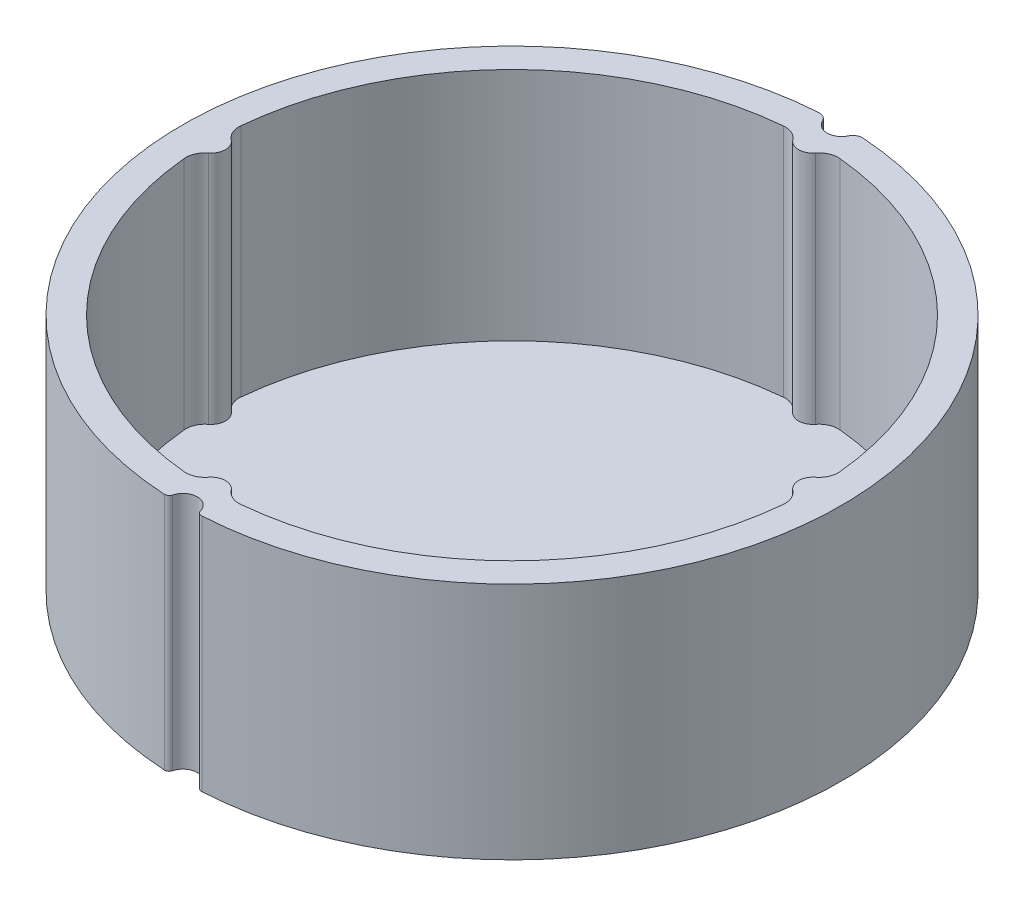
SolidWorks part; units mm, degrees
ref_plane "Front Plane" through (0, 0, 0) normal (0, 0, 1) x (1, 0, 0)
ref_plane "Top Plane" through (0, 0, 0) normal (0, 1, 0) x (1, 0, 0)
ref_plane "Right Plane" through (0, 0, 0) normal (1, 0, 0) x (0, 0, -1)
sketch "Sketch1" plane through (0, 0, 0) normal (0, 1, 0) x (1, 0, 0)
  line L3 (0, 0.002) -> (0, 3.7877) construction
  line L4 (0, 3.7877) -> (2.417, 3.7877)
  line L5 (0, 3.7877) -> (-2.417, 3.7877)
  arc A0 (1.9642, -34.442) -> (34.1982, 4.5552) centre (0, 0.002) ccw
  arc A2 (-2.417, 3.7877) -> (2.417, 3.7877) centre (0, 0.002) ccw
  circle A3 centre (0, 0.002) radius 34.5 construction
  arc A7 (-1.3541, 33.8562) -> (1.3541, 33.8562) centre (0, 34.5015) ccw
  arc A8 (34.1982, 4.5552) -> (2.3241, 34.4236) centre (0, 0.002) ccw
  arc A9 (-2.3241, 34.4236) -> (-34.1982, 4.5552) centre (0, 0.002) ccw
  arc A10 (-34.1982, 4.5552) -> (-1.9642, -34.442) centre (0, 0.002) ccw
  arc A11 (1.3541, 33.8562) -> (2.3241, 34.4236) centre (2.2568, 33.4259) cw
  arc A12 (-1.3541, 33.8562) -> (-2.3241, 34.4236) centre (-2.2568, 33.4259) ccw
  arc A13 (1.4518, -34.0686) -> (-1.4518, -34.0686) centre (0, -34.4457) ccw
  arc A14 (1.4518, -34.0686) -> (1.9642, -34.442) centre (1.9358, -33.9428) ccw
  arc A15 (-1.4518, -34.0686) -> (-1.9642, -34.442) centre (-1.9358, -33.9428) cw
  point P15 (1.4997, 34.4694)
  dimension "D2" = 4.834
  dimension "D3" = 4.4915
  dimension "D4" = 34.5
  dimension "D5" = 1
  dimension "D6" = 1.5
  dimension "D7" = 0.5
  dimension "D11" = 1.4997
sketch "Sketch2" plane through (0, 0, 0) normal (0, 1, 0) x (1, 0, 0)
  arc A0 (-31.3602, -2.9648) -> (-2.9648, -31.3602) centre (0, 0) ccw
  arc A1 (-1.1899, 30.5867) -> (1.1899, 30.5867) centre (0, 31.5) ccw
  arc A2 (30.5867, 1.1899) -> (30.5867, -1.1899) centre (31.5, 0) ccw
  arc A3 (1.1899, -30.5867) -> (-1.1899, -30.5867) centre (0, -31.5) ccw
  arc A4 (-30.5867, -1.1899) -> (-30.5867, 1.1899) centre (-31.5, 0) ccw
  arc A5 (-2.9648, 31.3602) -> (-31.3602, 2.9648) centre (0, 0) ccw
  arc A6 (31.3602, 2.9648) -> (2.9648, 31.3602) centre (0, 0) ccw
  arc A7 (2.9648, -31.3602) -> (31.3602, -2.9648) centre (0, 0) ccw
  arc A8 (-30.5867, -1.1899) -> (-31.3602, -2.9648) centre (-29.369, -2.7765) ccw
  arc A9 (-30.5867, 1.1899) -> (-31.3602, 2.9648) centre (-29.369, 2.7765) cw
  arc A10 (1.1899, -30.5867) -> (2.9648, -31.3602) centre (2.7765, -29.369) ccw
  arc A11 (-1.1899, -30.5867) -> (-2.9648, -31.3602) centre (-2.7765, -29.369) cw
  arc A12 (30.5867, 1.1899) -> (31.3602, 2.9648) centre (29.369, 2.7765) ccw
  arc A13 (30.5867, -1.1899) -> (31.3602, -2.9648) centre (29.369, -2.7765) cw
  arc A14 (1.1899, 30.5867) -> (2.9648, 31.3602) centre (2.7765, 29.369) cw
  arc A15 (-1.1899, 30.5867) -> (-2.9648, 31.3602) centre (-2.7765, 29.369) ccw
  point P21 (1.4996, -31.4643)
  point P26 (31.4643, 1.4996)
  point P33 (-1.4996, 31.4643)
  dimension "D1" = 31.5
  dimension "D2" = 1.5
  dimension "D6" = 2
extrude "Boss-Extrude1" add sketch "Sketch1" along normal blind 25 contours A10 A0 A8 A7 A9 A2 L5 L4 region at (2.2155, 0, 33.5591)
extrude "Cut-Extrude2" cut sketch "Sketch2" along normal through all
extrude "Boss-Extrude2" add sketch "Sketch2<2>" along normal blind 0.4
sketch "Sketch2<2>" plane through (0, 0, 0) normal (0, 1, 0) x (1, 0, 0) same geometry as "Sketch2"
